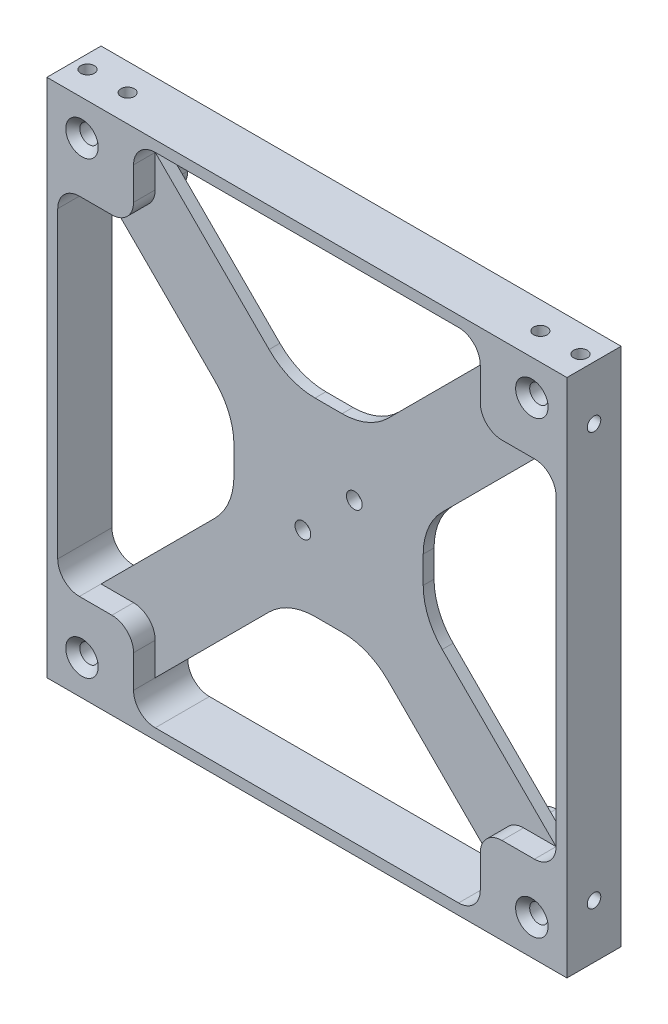
SolidWorks part; units mm, degrees
material "7075-T6 (SN)"
ref_plane "Front Plane" through (0, 0, 0) normal (0, 0, 1) x (1, 0, 0)
ref_plane "Top Plane" through (0, 0, 0) normal (0, 1, 0) x (1, 0, 0)
ref_plane "Right Plane" through (0, 0, 0) normal (1, 0, 0) x (0, 0, -1)
sketch "Construction Lines" plane through (0, 0, 0) normal (0, 0, 1) x (1, 0, 0)
  line L0 (0, 0) -> (0, -14.7163) construction
  line L1 (0, 0) -> (23.9312, 0) construction
sketch "Sketch3" plane through (0, 0, 0) normal (0, 0, 1) x (1, 0, 0)
  line L0 (0, 48) -> (48, 48)
  line L1 (0, 200000) -> (0, -200014.7163) construction
  line L2 (48, 48) -> (48, 0)
  line L3 (-200000, 0) -> (200023.9312, 0) construction
  line L4 (0, 46) -> (28, 46)
  line L5 (46, 28) -> (46, 0)
  line L6 (0, 48) -> (0, 46)
  line L7 (48, 0) -> (46, 0)
  line L8 (32, 42) -> (32, 36)
  line L9 (36, 32) -> (42, 32)
  line L11 (0, 46) -> (46, 46) construction
  line L12 (46, 46) -> (46, 0) construction
  arc A0 (28, 46) -> (32, 42) centre (28, 42) cw
  arc A1 (32, 36) -> (36, 32) centre (36, 36) ccw
  arc A2 (46, 28) -> (42, 32) centre (42, 28) ccw
  dimension "D6" = 4
  dimension "D1" = 48
  dimension "D2" = 48
  dimension "D4" = 16
  dimension "D5" = 16
  dimension "D3" = 2
extrude "BottomLayer" add sketch "Sketch3" along normal blind 4
sketch "TopHolePosition" plane through (0, 0, 4) normal (0, 0, 1) x (1, 0, 0)
  line L0 (0, 0) -> (48, 48) construction
sketch "Sketch6" plane through (0, 0, 4) normal (0, 0, 1) x (1, 0, 0)
  line L0 (0, 17.4706) -> (0, 0)
  line L1 (0, 0) -> (17.4706, 0)
  line L3 (0, 17.4706) -> (2.5, 17.4706)
  line L4 (0, 0) -> (48, 48) construction
  line L6 (17.4706, 0) -> (17.4706, 2.5)
  line L7 (38, 48) -> (10.9853, 20.9853)
  line L8 (48, 38) -> (20.9853, 10.9853)
  line L15 (48, 48) -> (0, 48) construction
  line L16 (48, 0) -> (48, 48) construction
  line L17 (38, 48) -> (48, 48)
  line L18 (48, 48) -> (48, 38)
  arc A1 (20.9853, 10.9853) -> (17.4706, 2.5) centre (29.4706, 2.5) ccw
  arc A2 (10.9853, 20.9853) -> (2.5, 17.4706) centre (2.5, 29.4706) cw
  dimension "D1" = 2.5
  dimension "D2" = 2.5
  dimension "D4" = 12
extrude "MiddleLayer" add sketch "Sketch6" along normal blind 2
sketch "Sketch10" plane through (0, 0, 6) normal (0, 0, 1) x (1, 0, 0)
  line L8 (48, 48) -> (0, 48)
  line L9 (48, 0) -> (48, 48)
  line L10 (46, 0) -> (48, 0)
  line L11 (46, 28) -> (46, 0)
  line L12 (36, 32) -> (42, 32)
  line L13 (32, 42) -> (32, 36)
  line L14 (0, 46) -> (28, 46)
  line L15 (0, 48) -> (0, 46)
  line L16 (48, 48) -> (0, 48)
  line L17 (48, 0) -> (48, 48)
  line L18 (46, 0) -> (48, 0)
  line L19 (46, 28) -> (46, 0)
  line L20 (36, 32) -> (42, 32)
  line L21 (32, 42) -> (32, 36)
  line L22 (0, 46) -> (28, 46)
  line L23 (0, 48) -> (0, 46)
  arc A3 (46, 28) -> (42, 32) centre (42, 28) ccw
  arc A4 (46, 28) -> (42, 32) centre (42, 28) ccw
  arc A5 (32, 36) -> (36, 32) centre (36, 36) ccw
  arc A6 (32, 36) -> (36, 32) centre (36, 36) ccw
  arc A7 (32, 42) -> (28, 46) centre (28, 42) ccw
  arc A8 (32, 42) -> (28, 46) centre (28, 42) ccw
  dimension "D1" = 0
extrude "FillUpLayer" add sketch "Sketch10" against normal blind 2
sketch "Sketch11" plane through (0, 0, 6) normal (0, 0, 1) x (1, 0, 0)
  line L8 (48, 48) -> (0, 48)
  line L9 (48, 0) -> (48, 48)
  line L10 (46, 0) -> (48, 0)
  line L11 (46, 28) -> (46, 0)
  line L12 (36, 32) -> (42, 32)
  line L13 (32, 42) -> (32, 36)
  line L14 (0, 46) -> (28, 46)
  line L15 (0, 48) -> (0, 46)
  line L16 (48, 48) -> (0, 48)
  line L17 (48, 0) -> (48, 48)
  line L18 (46, 0) -> (48, 0)
  line L19 (46, 28) -> (46, 0)
  line L20 (36, 32) -> (42, 32)
  line L21 (32, 42) -> (32, 36)
  line L22 (0, 46) -> (28, 46)
  line L23 (0, 48) -> (0, 46)
  arc A3 (46, 28) -> (42, 32) centre (42, 28) ccw
  arc A4 (46, 28) -> (42, 32) centre (42, 28) ccw
  arc A5 (32, 36) -> (36, 32) centre (36, 36) ccw
  arc A6 (32, 36) -> (36, 32) centre (36, 36) ccw
  arc A7 (32, 42) -> (28, 46) centre (28, 42) ccw
  arc A8 (32, 42) -> (28, 46) centre (28, 42) ccw
  dimension "D1" = 0
extrude "TopLayer" add sketch "Sketch11" along normal blind 4
sketch "HolePosition" plane through (0, 0, 10) normal (0, 0, 1) x (1, 0, 0)
  line L0 (0, 41.525) -> (41.525, 41.525) construction
  line L1 (0, 200000) -> (0, -200014.7163) construction
  line L2 (0, 0) -> (48, 48) construction
  line L3 (41.525, 41.525) -> (41.525, 0) construction
  line L4 (-200000, 0) -> (200023.9312, 0) construction
  dimension "D1" = 41.525
hole_wizard "M3 Clearance Hole1" positions "Sketch13" profile "Sketch14" hole size "M3" standard "ISO" end condition through all
sketch "Sketch13" plane through (0, 0, 10) normal (0, 0, 1) x (1, 0, 0)
  point P0 (41.525, 41.525)
sketch "Sketch14" plane through (41.525, 41.525, 10) normal (1, 0, 0) x (0, -1, 0)
  line L0 (0, 0) -> (0, 10)
  line L1 (0, 10) -> (1.7, 10)
  line L2 (1.7, 10) -> (1.7, 1.3)
  line L3 (1.7, 1.3) -> (3, 0)
  line L5 (3, 0) -> (0, 0)
  line L6 (-1.7, 1.3) -> (-3, 0) construction
  line L11 (0, -6.35) -> (0, 107.95) construction
  dimension "Thru Hole Dia." = 3.4
  dimension "Thru Hole Depth" = 10
  dimension "Near C'Sink Dia." = 6
  dimension "Near C'Sink Angle" = 90
ref_axis "Axis1" through (0, 0, -0.5) along (0, 0, 1)
sketch "M2HolePositions" plane through (0, 0, 6) normal (0, 0, 1) x (1, 0, 0)
  line L0 (0, 0) -> (48, 48) construction
  line L1 (0, 200000) -> (0, -200014.7163) construction
  line L2 (0, 0) -> (6.9513, -6.9513) construction
  line L3 (-200000, 0) -> (200023.9312, 0) construction
  line L4 (0, 4.75) -> (4.75, 4.75) construction
  line L5 (4.75, 4.75) -> (4.75, 0) construction
  dimension "D1" = 45
  dimension "D3" = 4.75
hole_wizard "M2.5 Clearance Hole1" positions "Sketch24" profile "Sketch25" hole size "M2.5" standard "ISO" end condition through all
sketch "Sketch24" plane through (0, 0, 6) normal (0, 0, 1) x (1, 0, 0)
  point P0 (4.75, 4.75)
sketch "Sketch25" plane through (4.75, 4.75, 6) normal (1, 0, 0) x (0, -1, 0)
  line L0 (0, 0) -> (0, 6)
  line L1 (0, 6) -> (1.45, 6)
  line L2 (1.45, 6) -> (1.45, 0)
  line L5 (1.45, 0) -> (0, 0)
  line L11 (0, -6.35) -> (0, 107.95) construction
  dimension "Thru Hole Dia." = 2.9
  dimension "Thru Hole Depth" = 6
pattern_circular "CirPattern1" count 4 every 90 about axis through (0, 0, -0.5) along (0, 0, 1) of "TopLayer", "FillUpLayer", "MiddleLayer", "BottomLayer", "M3 Clearance Hole1"
sketch "SidePlate Hole ZY" plane through (48, 0, 0) normal (1, 0, 0) x (0, 0, -1)
  line L0 (-5, 48) -> (-5, -48) construction
  line L1 (-10, 48) -> (0, 48) construction
  line L2 (-10, -48) -> (0, -48) construction
  line L3 (-10, 38.1) -> (-5, 38.1) construction
  line L4 (-10, -48) -> (-10, 48) construction
  dimension "D1" = 9.9
sketch "SidePlate&RailHole ZX" plane through (0, 48, 0) normal (0, 1, 0) x (1, 0, 0)
  line L0 (48, -5) -> (-48, -5) construction
  line L1 (-48, -10) -> (-48, 0) construction
  line L2 (45.5, -10) -> (45.5, -5) construction
  line L5 (48, -10) -> (-48, -10) construction
  line L7 (38.1, -10) -> (38.1, -5) construction
  line L8 (48, -10) -> (48, 0) construction
  dimension "D1" = 2.5
  dimension "D2" = 9.9
hole_wizard "Tap Drill M3 Side Plate" positions "Sketch20" profile "Sketch21" hole size "M3" standard "ISO"
sketch "Sketch20" plane through (48, 0, 0) normal (1, 0, 0) x (0, 0, -1)
  point P0 (-5, 38.1)
sketch "Sketch21" plane through (48, 38.1, 5) normal (0, 1, 0) x (0, 0, -1)
  line L0 (0, 0) -> (0, 5.7511)
  line L1 (0, 5.7511) -> (1.25, 5)
  line L2 (1.25, 5) -> (1.25, 0)
  line L5 (1.25, 0) -> (0, 0)
  line L10 (0, 5.7511) -> (-1.25, 5) construction
  line L11 (0, -6.35) -> (0, 107.95) construction
  dimension "Hole Dia." = 2.5
  dimension "Hole Depth" = 5
  dimension "Drill Angle" = 118
ref_plane "MirrorPlaneForM2.5" through (0, 0, 0) normal (-0.7071, -0.7071, 0) x (0.7071, -0.7071, 0)
mirror "Camera Holes" about plane through (0, 0, 0) normal (-0.7071, -0.7071, 0) of "M2.5 Clearance Hole1"
hole_wizard "Tap Drill M3 Side Plate " positions "Sketch26" profile "Sketch27" hole size "M3" standard "ISO"
sketch "Sketch26" plane through (0, 48, 0) normal (0, 1, 0) x (1, 0, 0)
  point P0 (38.1, -5)
sketch "Sketch27" plane through (38.1, 48, 5) normal (1, 0, 0) x (0, 0, 1)
  line L0 (0, 0) -> (0, 5.7511)
  line L1 (0, 5.7511) -> (1.25, 5)
  line L2 (1.25, 5) -> (1.25, 0)
  line L5 (1.25, 0) -> (0, 0)
  line L10 (0, 5.7511) -> (-1.25, 5) construction
  line L11 (0, -6.35) -> (0, 107.95) construction
  dimension "Hole Dia." = 2.5
  dimension "Hole Depth" = 5
  dimension "Drill Angle" = 118
hole_wizard "Tap Drill M3 Rail" positions "Sketch28" profile "Sketch29" hole size "M3" standard "ISO"
sketch "Sketch28" plane through (0, 48, 0) normal (0, 1, 0) x (1, 0, 0)
  point P0 (45.5, -5)
sketch "Sketch29" plane through (45.5, 48, 5) normal (1, 0, 0) x (0, 0, 1)
  line L0 (0, 0) -> (0, 5.7511)
  line L1 (0, 5.7511) -> (1.25, 5)
  line L2 (1.25, 5) -> (1.25, 0)
  line L5 (1.25, 0) -> (0, 0)
  line L10 (0, 5.7511) -> (-1.25, 5) construction
  line L11 (0, -6.35) -> (0, 107.95) construction
  dimension "Hole Dia." = 2.5
  dimension "Hole Depth" = 5
  dimension "Drill Angle" = 118
mirror "SidePlate and Rail Holes 1" about plane through (0, 0, 0) normal (1, 0, 0) of "Tap Drill M3 Side Plate", "Tap Drill M3 Rail", "Tap Drill M3 Side Plate "
mirror "Side Plate and Rail Holes 2" about plane through (0, 0, 0) normal (0, 1, 0) of "SidePlate and Rail Holes 1"
sketch "Sketch30" plane through (0, 0, 0) normal (0, 0, -1) x (-1, 0, 0)
  circle A0 centre (-41.525, 41.525) radius 2.7
  point P0 (-41.525, 41.525)
extrude "Cut-Extrude1" cut sketch "Sketch30" against normal blind 3.4
pattern_circular "CirPattern2" count 4 over 360 about axis through (0, 0, -0.5) along (0, 0, 1) of "Cut-Extrude1"
